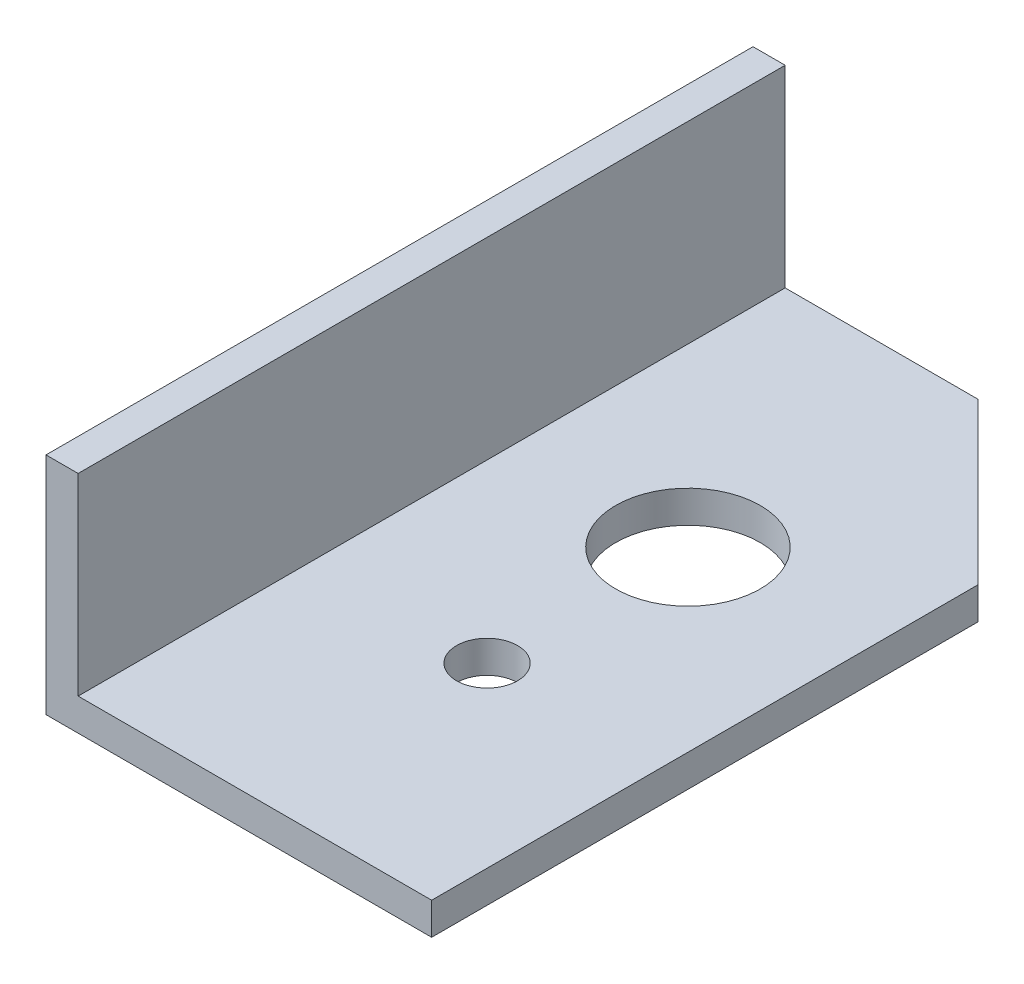
SolidWorks part; units mm, degrees
ref_plane "Спереди" through (0, 0, 0) normal (0, 0, 1) x (1, 0, 0)
ref_plane "Сверху" through (0, 0, 0) normal (0, 1, 0) x (1, 0, 0)
ref_plane "Справа" through (0, 0, 0) normal (1, 0, 0) x (0, 0, -1)
sketch "Эскиз2" plane through (0, 0, 0) normal (0, 0, 1) x (1, 0, 0)
  line L0 (0, 0) -> (0, 14)
  line L1 (0, 0) -> (24, 0)
extrude "Вытянуть-Тонкостенный1" add sketch "Эскиз2" along normal blind 44 thin thin type one direction reverse wall 2
chamfer "Фаска1" distance 10 angle 45 1 edges at (24, 1, 0)
sketch "Эскиз4" plane through (0, 2, 0) normal (0, 1, 0) x (-1, 0, 0)
  line L0 (-2, 22) -> (14.8253, 22) construction
  circle A2 centre (-12.95, 17) radius 4.5
  circle A3 centre (-12.95, 29.5) radius 1.9
extrude "Вырез-Вытянуть1" cut sketch "Эскиз4" against normal through all
